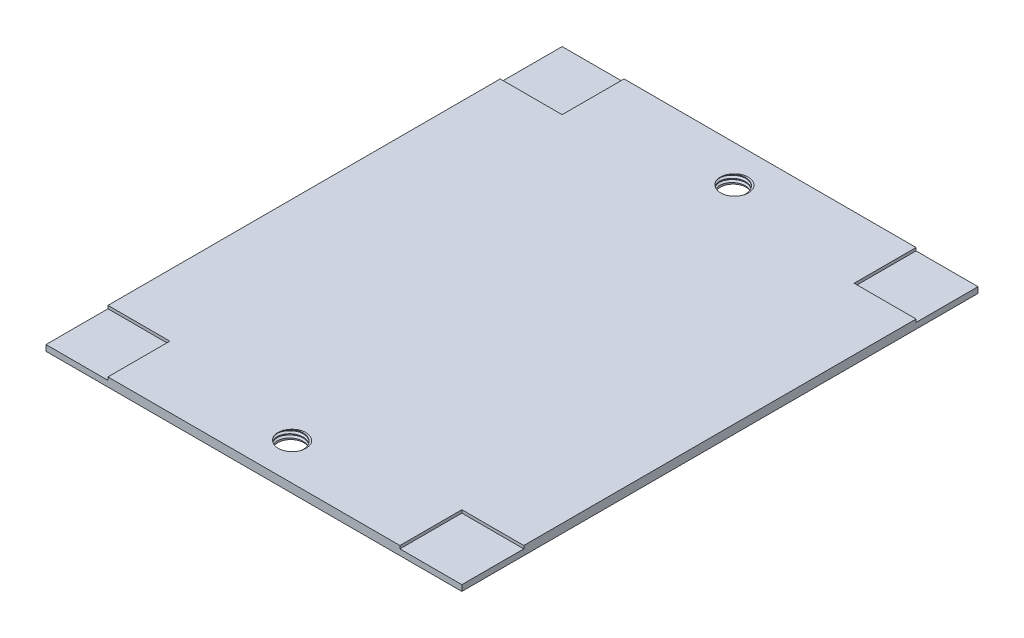
SolidWorks part; units mm, degrees
ref_plane "Front Plane" through (0, 0, 0) normal (0, 0, 1) x (1, 0, 0)
ref_plane "Top Plane" through (0, 0, 0) normal (0, 1, 0) x (1, 0, 0)
ref_plane "Right Plane" through (0, 0, 0) normal (1, 0, 0) x (0, 0, -1)
sketch "Sketch1" plane through (0, 0, 0) normal (0, 1, 0) x (1, 0, 0)
  line L1 (-141, -175) -> (141, -175)
  line L2 (-141, -175) -> (-141, 175)
  line L3 (-141, 175) -> (141, 175)
  line L4 (141, -175) -> (141, 175)
  line L5 (-141, -175) -> (141, 175) construction
  line L6 (-141, 175) -> (141, -175) construction
  point P0 (0, 0)
  dimension "D1" = 282
  dimension "D2" = 350
extrude "Boss-Extrude1" add sketch "Sketch1" along normal blind 6
sketch "Sketch2" plane through (0, 6, 0) normal (0, 1, 0) x (1, 0, 0)
  line L0 (-141, -175) -> (141, -175) construction
  line L1 (-141, 175) -> (-99, 175)
  line L2 (-141, 175) -> (-141, 133)
  line L3 (-141, 133) -> (-99, 133)
  line L4 (-99, 175) -> (-99, 133)
  line L5 (141, 175) -> (99, 175)
  line L6 (141, 175) -> (141, 133)
  line L7 (141, 133) -> (99, 133)
  line L8 (99, 175) -> (99, 133)
  line L9 (-141, -175) -> (-99, -175)
  line L10 (-141, -175) -> (-141, -133)
  line L11 (-141, -133) -> (-99, -133)
  line L12 (-99, -175) -> (-99, -133)
  line L13 (141, -175) -> (99, -175)
  line L14 (141, -175) -> (141, -133)
  line L15 (141, -133) -> (99, -133)
  line L16 (99, -175) -> (99, -133)
  point P20 (141, -187.0307)
  dimension "D1" = 42
  dimension "D2" = 42
  dimension "D3" = 42
  dimension "D4" = 42
  dimension "D5" = 42
  dimension "D6" = 42
extrude "Cut-Extrude1" cut sketch "Sketch2" against normal blind 2
sketch "Sketch3" plane through (0, 6, 0) normal (0, 1, 0) x (1, 0, 0)
  line L0 (0, -150) -> (0, 150)
  circle A0 centre (0, 150) radius 8.75
  circle A1 centre (0, -150) radius 8.75
  point P4 (0, 0)
  dimension "D2" = 17.5
  dimension "D3" = 17.5
  dimension "D1" = 300
extrude "Cut-Extrude2" cut sketch "Sketch3" against normal blind 10 contours A0 | A1 region at (-6.0122, 6, -156.0122)
thread "Thread1" pitch 2.5 method cut profile "Thread Profile2" start angle 0, offset 0, length 15, pitch 2.5, diameter 17.5
ref_plane "Plane2" through (8.75, 0, -150) normal (0, 0, 1) x (1, 0, 0)
sketch "Thread Profile2" plane through (8.75, 0, -150) normal (0, 0, 1) x (1, 0, 0)
  line L0 (0, 0) -> (0, 2.5) construction
  line L1 (0, 0) -> (1.3532, 0.7812)
  line L2 (1.3532, 0.7812) -> (1.3532, 1.0937)
  line L3 (1.3532, 1.0937) -> (0, 1.875)
  line L4 (1.3532, 0.9375) -> (0, 0.9375) construction
  line L11 (0, 0) -> (0, 1.875)
  point P2 (0, 0)
  dimension "Pitch" = 2.5
  dimension "Profile_Angle" = 60
  dimension "Profile_Land" = 0.3125
  dimension "Profile_Height" = 1.3532
thread "Thread2" pitch 2.5 method cut profile "Thread Profile3" start angle 0, offset 0, length 15, pitch 2.5, diameter 17.5
ref_plane "Plane3" through (8.75, 0, 150) normal (0, 0, 1) x (1, 0, 0)
sketch "Thread Profile3" plane through (8.75, 0, 150) normal (0, 0, 1) x (1, 0, 0)
  line L0 (0, 0) -> (0, 2.5) construction
  line L1 (0, 0) -> (1.3532, 0.7812)
  line L2 (1.3532, 0.7812) -> (1.3532, 1.0937)
  line L3 (1.3532, 1.0937) -> (0, 1.875)
  line L4 (1.3532, 0.9375) -> (0, 0.9375) construction
  line L11 (0, 0) -> (0, 1.875)
  point P2 (0, 0)
  dimension "Pitch" = 2.5
  dimension "Profile_Angle" = 60
  dimension "Profile_Land" = 0.3125
  dimension "Profile_Height" = 1.3532
